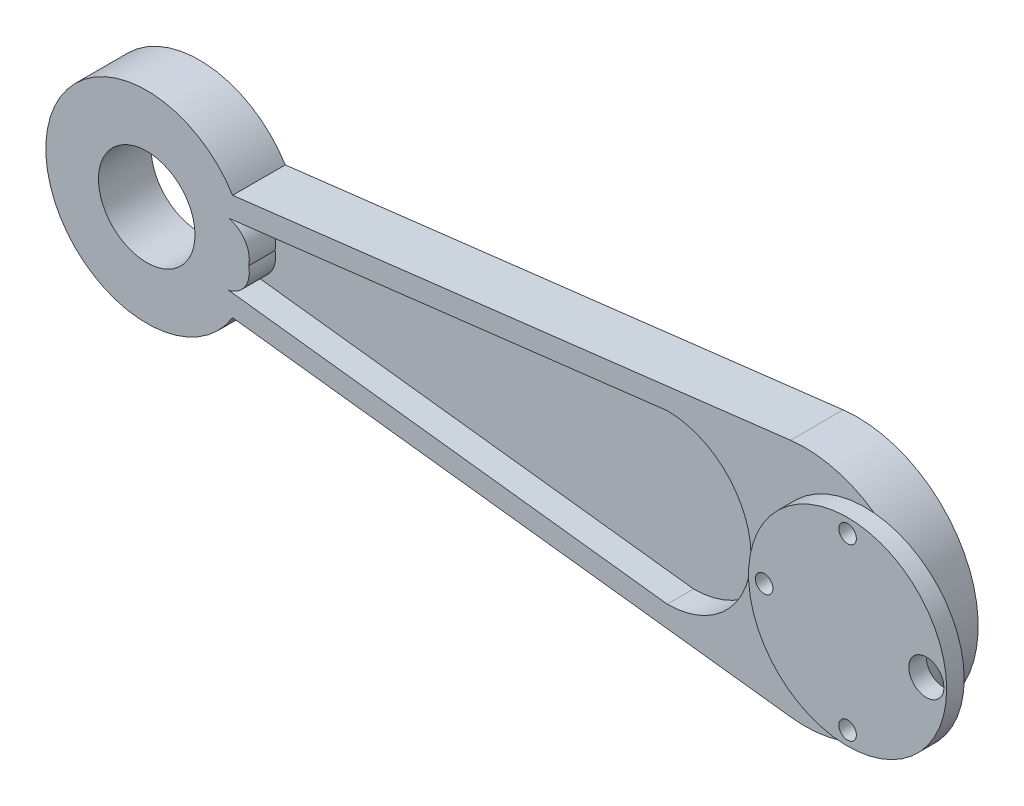
SolidWorks part; units mm, degrees
ref_plane "Front Plane" through (0, 0, 0) normal (0, 0, 1) x (1, 0, 0)
ref_plane "Top Plane" through (0, 0, 0) normal (0, 1, 0) x (1, 0, 0)
ref_plane "Right Plane" through (0, 0, 0) normal (1, 0, 0) x (0, 0, -1)
sketch "Sketch1" plane through (0, 0, 0) normal (0, 0, 1) x (1, 0, 0)
  line L0 (-140.3042, 0) -> (9.6958, 0) construction
  line L1 (6.426, 27.3049) -> (-120.7306, 12.0777)
  line L2 (6.426, -27.3049) -> (-120.7306, -12.0777)
  arc A0 (-120.7306, 12.0777) -> (-120.7306, -12.0777) centre (-140.3042, 0) ccw
  arc A1 (6.426, -27.3049) -> (6.426, 27.3049) centre (9.6958, 0) ccw
  dimension "D1" = 46
  dimension "D3" = 55
  dimension "D2" = 150
extrude "Boss-Extrude1" add sketch "Sketch1" along normal blind 12
sketch "Sketch3" plane through (0, 0, 12) normal (0, 0, 1) x (1, 0, 0)
  line L0 (-121.6703, 7.1224) -> (-21.679, 19.0965)
  line L1 (-120.7306, 12.0777) -> (6.426, 27.3049) construction
  line L2 (-141.2244, 0) -> (0, 0) construction
  line L3 (-121.6703, -7.1224) -> (-21.679, -19.0965)
  arc A0 (-21.679, -19.0965) -> (-21.679, 19.0965) centre (-21.6703, 0) ccw
  arc A1 (-121.6703, 7.1224) -> (-117.0591, 0) centre (-122.9259, 1.2556) cw
  arc A2 (-121.6703, -7.1224) -> (-117.0591, 0) centre (-122.9259, -1.2556) ccw
extrude "Cut-Extrude1" cut sketch "Sketch3" against normal blind 6 contours L3 A0 L0 A1 A2
sketch "Sketch4" plane through (0, 0, 12) normal (0, 0, 1) x (1, 0, 0)
  circle A0 centre (-140.3042, 0) radius 11
  dimension "D1" = 22
extrude "Cut-Extrude2" cut sketch "Sketch4" against normal blind 12 contours A0
sketch "Sketch5" plane through (0, 0, 12) normal (0, 0, 1) x (1, 0, 0)
  circle A2 centre (23.4332, 0) radius 22.58
extrude "Boss-Extrude2" add sketch "Sketch5" along normal blind 4
sketch "Sketch6" plane through (0, 0, 16) normal (0, 0, 1) x (1, 0, 0)
  line L0 (23.4332, 22.58) -> (23.4332, -22.58) construction
  line L1 (0.8533, 0) -> (46.0132, 0) construction
  circle A0 centre (23.4332, 0) radius 22.58 construction
  arc A1 (25.5325, 22.4822) -> (25.5325, -22.4822) centre (23.4332, 0) ccw construction
  circle A2 centre (4.4167, 0) radius 2
  circle A3 centre (4.4167, 0) radius 2
  circle A4 centre (4.4167, 0) radius 2
  circle A5 centre (23.4332, -19.3923) radius 2
  circle A6 centre (42.4498, 0) radius 2
  circle A7 centre (23.4332, 19.3923) radius 2
  dimension "D1" = 4
  dimension "D2" = 4
  dimension "D3" = 3.5634
extrude "Cut-Extrude3" cut sketch "Sketch6" against normal blind 16 contours A2
extrude "Cut-Extrude5" cut sketch "Sketch6<3>" against normal blind 16 contours A5 | A6 | A7 region at (23.4332, -19.3923, 16) region at (42.4498, 0, 16)
sketch "Sketch6<3>" plane through (0, 0, 16) normal (0, 0, 1) x (1, 0, 0) same geometry as "Sketch6"
sketch "Sketch7" plane through (0, 0, 16) normal (0, 0, 1) x (1, 0, 0)
  circle A0 centre (41.3773, 0) radius 4
  dimension "D1" = 8
extrude "Cut-Extrude6" cut sketch "Sketch7" against normal through all both
